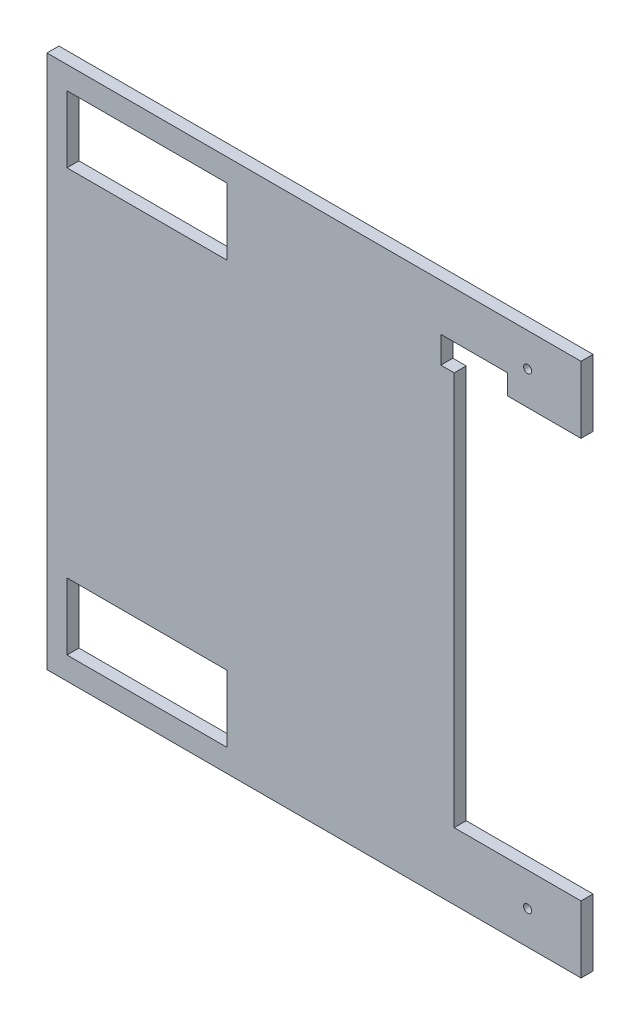
SolidWorks part; units mm, degrees
material "Pine"
ref_plane "Front Plane" through (0, 0, 0) normal (0, 0, 1) x (1, 0, 0)
ref_plane "Top Plane" through (0, 0, 0) normal (0, 1, 0) x (1, 0, 0)
ref_plane "Right Plane" through (0, 0, 0) normal (1, 0, 0) x (0, 0, -1)
sketch "Sketch1" plane through (0, 0, 0) normal (0, 0, 1) x (1, 0, 0)
  line L0 (0, -400) -> (0, 0)
  line L1 (0, 0) -> (-400, 0)
  line L2 (-400, 0) -> (-400, -400)
  line L3 (-400, -400) -> (0, -400)
  line L9 (-385, -17) -> (-265, -17)
  line L10 (-385, -17) -> (-385, -67)
  line L11 (-385, -67) -> (-265, -67)
  line L12 (-265, -17) -> (-265, -67)
  line L13 (-385, -17) -> (-265, -67) construction
  line L14 (-385, -67) -> (-265, -17) construction
  line L18 (-385, -383) -> (-265, -383)
  line L19 (-385, -383) -> (-385, -333)
  line L20 (-385, -333) -> (-265, -333)
  line L21 (-265, -383) -> (-265, -333)
  line L22 (-385, -383) -> (-265, -333) construction
  line L23 (-385, -333) -> (-265, -383) construction
  point P16 (-325, -42)
  point P27 (-325, -358)
  dimension "D1" = 120
  dimension "D2" = 50
  dimension "D3" = 17
  dimension "D4" = 120
  dimension "D5" = 15
  dimension "D6" = 15
  dimension "D7" = 50
  dimension "D8" = 17
  dimension "D9" = 400
  dimension "D10" = 400
extrude "Boss-Extrude1" add sketch "Sketch1" along normal blind 9
sketch "Sketch2" plane through (0, 0, 0) normal (0, 0, -1) x (-1, 0, 0)
  line L0 (95, -350) -> (95, -50)
  line L1 (0, 0) -> (95, 0)
  line L2 (0, 0) -> (0, -50)
  line L3 (0, -50) -> (95, -50)
  line L4 (95, 0) -> (95, -50)
  line L5 (0, 0) -> (95, -50) construction
  line L6 (0, -50) -> (95, 0) construction
  line L7 (0, -400) -> (95, -400)
  line L8 (0, -400) -> (0, -350)
  line L9 (0, -350) -> (95, -350)
  line L10 (95, -400) -> (95, -350)
  line L11 (0, -400) -> (95, -350) construction
  line L12 (0, -350) -> (95, -400) construction
  point P4 (47.5, -25)
  point P10 (47.5, -375)
  line M11 (0, 0) -> (0, -400)
  dimension "D1" = 50
  dimension "D2" = 50
  dimension "D3" = 95
extrude "Cut-Extrude1" cut sketch "Sketch2" against normal through all contours L9 L0 L3 M11 region at (-47.5, -200, 0)
sketch "Sketch3" plane through (0, 0, 0) normal (0, 0, -1) x (-1, 0, 0)
  line L1 (95, -50) -> (55, -50)
  line L2 (95, -50) -> (95, -35)
  line L3 (95, -35) -> (55, -35)
  line L4 (55, -50) -> (55, -35)
  dimension "D1" = 40
  dimension "D2" = 15
extrude "Cut-Extrude2" cut sketch "Sketch3" against normal blind 10
sketch "Sketch4" plane through (0, 0, 0) normal (0, 0, -1) x (-1, 0, 0)
  line L1 (95, -35) -> (105, -35)
  line L2 (95, -35) -> (95, -55)
  line L3 (95, -55) -> (105, -55)
  line L4 (105, -35) -> (105, -55)
  dimension "D1" = 10
  dimension "D2" = 20
extrude "Cut-Extrude3" cut sketch "Sketch4" against normal blind 100
sketch "Sketch5" plane through (0, 0, 0) normal (0, 0, -1) x (-1, 0, 0)
  line L0 (0, -50) -> (0, 0) construction
  line L1 (0, 0) -> (400, 0) construction
  line L2 (0, -400) -> (0, -350) construction
  line L3 (400, -400) -> (0, -400) construction
  circle A0 centre (40, -25) radius 3
  circle A1 centre (40, -375) radius 3
  dimension "D1" = 40
  dimension "D2" = 25
  dimension "D3" = 6
  dimension "D4" = 40
  dimension "D5" = 25
  dimension "D6" = 6
extrude "Cut-Extrude4" cut sketch "Sketch5" against normal through all
